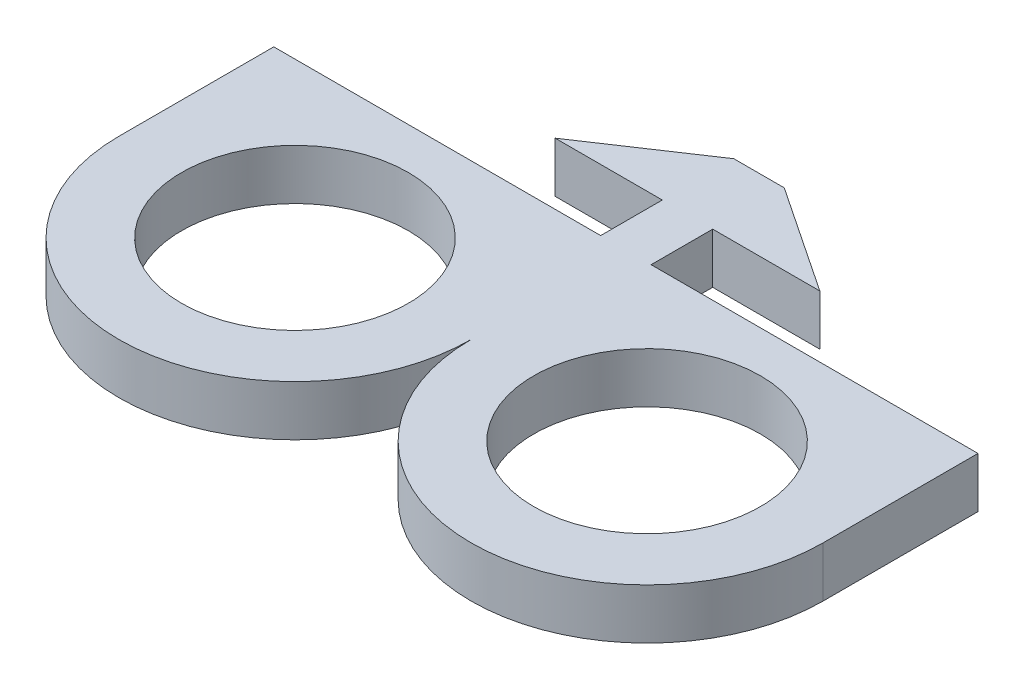
SolidWorks part; units mm, degrees
ref_plane "Front" through (0, 0, 0) normal (0, 0, 1) x (1, 0, 0)
ref_plane "Top" through (0, 0, 0) normal (0, 1, 0) x (1, 0, 0)
ref_plane "Right" through (0, 0, 0) normal (1, 0, 0) x (0, 0, -1)
sketch "Sketch1" plane through (0, 0, 0) normal (0, 1, 0) x (1, 0, 0)
  line L0 (-1.7907, 2.1875) -> (-9.398, 2.1875)
  line L2 (-1.7907, -2.1875) -> (-1.7907, 2.1875)
  line L4 (1.7907, -2.1875) -> (1.7907, 2.1875)
  line L7 (-9.398, 2.1875) -> (-1.7907, 7.2675)
  line L8 (-1.7907, 7.2675) -> (1.7907, 7.2675)
  line L9 (1.7907, 7.2675) -> (9.398, 2.1875)
  line L10 (9.398, 2.1875) -> (1.7907, 2.1875)
  line L11 (1.7907, -2.1875) -> (25.0063, -2.1875)
  line L12 (-1.7907, -2.1875) -> (-25.0063, -2.1875)
  line L13 (-25.0063, -2.1875) -> (-25.0063, -13.1857)
  line L14 (-25.0063, -13.1857) -> (25.0063, -13.1857)
  line L15 (25.0063, -13.1857) -> (25.0063, -2.1875)
  line L16 (25.0063, -2.1875) -> (1.7907, -2.1875)
  point P0 (0, 0)
  point P17 (0, 7.2675)
  point P19 (0, -13.1857)
  point P24 (1.7907, 0)
  dimension "D1" = 18.796
  dimension "D2" = 3.5814
  dimension "D3" = 50.0126
  dimension "D4" = 10.9982
  dimension "D5" = 5.08
  dimension "D7" = 4.375
extrude "Boss-Extrude1" add sketch "Sketch1" along normal blind 3.5814 contours L14 L15 L11 L4 L10 L9 L8 L7 L0 L2 L12 L13 region at (0, 0, 6.4123)
sketch "Sketch3" plane through (0, 3.5814, 0) normal (0, 1, 0) x (1, 0, 0)
  line L3 (-25.0063, -13.1857) -> (25.0063, -13.1857) construction
  line L16 (-25.0063, -13.1857) -> (25.0063, -13.1857)
  line L17 (25.0063, -13.1857) -> (25.0063, -2.1875)
  line L18 (25.0063, -2.1875) -> (1.7907, -2.1875)
  line L19 (1.7907, -2.1875) -> (1.7907, 2.1875)
  line L20 (1.7907, 2.1875) -> (9.398, 2.1875)
  line L21 (9.398, 2.1875) -> (1.7907, 7.2675)
  line L22 (1.7907, 7.2675) -> (-1.7907, 7.2675)
  line L23 (-1.7907, 7.2675) -> (-9.398, 2.1875)
  line L24 (-9.398, 2.1875) -> (-1.7907, 2.1875)
  line L25 (-1.7907, 2.1875) -> (-1.7907, -2.1875)
  line L26 (-1.7907, -2.1875) -> (-25.0063, -2.1875)
  line L27 (-25.0063, -2.1875) -> (-25.0063, -13.1857)
  line L28 (-25.0063, -13.1857) -> (25.0063, -13.1857)
  arc A2 (-25.0063, -13.1857) -> (0, -13.1857) centre (-12.5031, -13.1857) ccw
  arc A3 (0, -13.1857) -> (25.0063, -13.1857) centre (12.5032, -13.1857) ccw
  line M15 (-25.0063, -13.1857) -> (25.0063, -13.1857)
  dimension "D1" = 0
extrude "Boss-Extrude2" add sketch "Sketch3" against normal up to surface (3.5814 mm away) contours A2 M15 | L28 A3 region at (-12.5031, 3.5814, 18.4922) region at (12.5032, 3.5814, 18.4922) up to face at (0, 0, 0.9864)
sketch "Sketch4" plane through (0, 3.5814, 0) normal (0, 1, 0) x (1, 0, 0)
  circle A0 centre (-12.5031, -13.1857) radius 8.0518
  circle A1 centre (12.5032, -13.1857) radius 8.0518
  arc A2 (-25.0063, -13.1857) -> (0, -13.1857) centre (-12.5031, -13.1857) ccw construction
  arc A3 (0, -13.1857) -> (25.0063, -13.1857) centre (12.5032, -13.1857) ccw construction
  dimension "D1" = 16.1036
extrude "Cut-Extrude2" cut sketch "Sketch4" against normal through all
